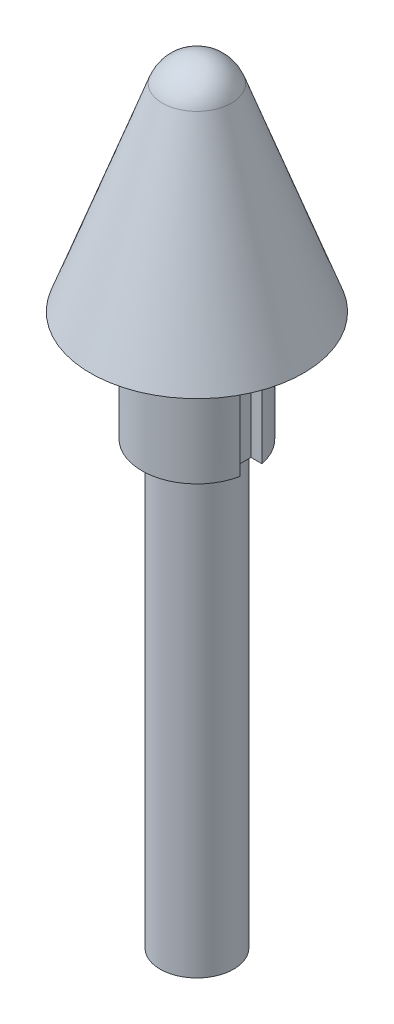
SolidWorks part; units mm, degrees
material "1023 Carbon Steel Sheet (SS)"
ref_plane "Front Plane" through (0, 0, 0) normal (0, 0, 1) x (1, 0, 0)
ref_plane "Top Plane" through (0, 0, 0) normal (0, 1, 0) x (1, 0, 0)
ref_plane "Right Plane" through (0, 0, 0) normal (1, 0, 0) x (0, 0, -1)
ref_axis "Axis1" through (0, -160.1892, 0) along (0, 1, 0)
sketch "Sketch1" plane through (0, 0, 0) normal (0, 0, 1) x (1, 0, 0)
  line L0 (0, -150) -> (15, -150)
  line L1 (0, -160.1892) -> (0, 55) construction
  line L2 (15, -150) -> (15, 0)
  line L3 (15, 0) -> (29, 0)
  line L4 (9.3969, 53.859) -> (29, 0)
  line L5 (0, 60.4388) -> (0, -150)
  line L6 (0, 60.4388) -> (46.473, 60.4388) construction
  arc A0 (0, 60.4388) -> (9.3969, 53.859) centre (0, 50.4388) cw
  dimension "D5" = 10
  dimension "D1" = 20
  dimension "D2" = 15
  dimension "D3" = 150
  dimension "D4" = 29
revolve "Revolve1" add sketch "Sketch1" angle 360 about axis through (0, -160.1892, 0) along (0, 1, 0)
sketch "Sketch2" plane through (0, 0, 0) normal (0, 0, 1) x (1, 0, 0)
  line L0 (15, -150) -> (15, 0) construction
  line L1 (15, -30) -> (10, -30)
  line L2 (15, -30) -> (15, -150)
  line L3 (15, -150) -> (10, -150)
  line L4 (10, -30) -> (10, -150)
  line L5 (-15, -150) -> (15, -150) construction
  line L6 (0, 9.4212) -> (0, -39.2525) construction
  line L7 (0, -160.1892) -> (0, 55) construction
  line L9 (55, 0) -> (-55, 0) construction
  dimension "D1" = 20
  dimension "D2" = 30
revolve "Cut-Revolve1" cut sketch "Sketch2" angle 360 about L6
sketch "Sketch3" plane through (0, -30, 0) normal (0, -1, 0) x (1, 0, 0)
  line L0 (14.6969, 3) -> (11.6969, 3)
  line L1 (11.6969, 3) -> (11.6969, -3)
  line L2 (11.6969, -3) -> (14.6969, -3)
  line L3 (15.8522, 0) -> (10.4119, 0) construction
  arc A0 (14.6969, 3) -> (14.6969, -3) centre (0, 0) cw
  circle A1 centre (0, 0) radius 15 construction
  dimension "D1" = 3
  dimension "D2" = 6
extrude "Cut-Extrude1" cut sketch "Sketch3" against normal blind 25
fillet "Fillet1" radius 3 2 edges at (13.1969, -5, 3) (13.1969, -5, -3)
